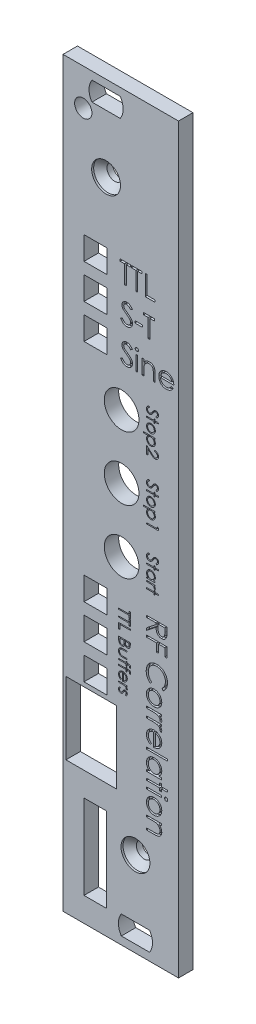
SolidWorks part; units mm, degrees
ref_plane "Front Plane" through (0, 0, 0) normal (0, 0, 1) x (1, 0, 0)
ref_plane "Top Plane" through (0, 0, 0) normal (0, 1, 0) x (1, 0, 0)
ref_plane "Right Plane" through (0, 0, 0) normal (1, 0, 0) x (0, 0, -1)
ref_plane "Plane1" through (0, 0, 2.5) normal (0, 0, 1) x (1, 0, 0)
sketch "Sketch1" plane through (0, 0, 2.5) normal (0, 0, 1) x (1, 0, 0)
  line L0 (12.53, 125.4) -> (-7.45, 125.4)
  line L1 (-7.45, 125.4) -> (-7.45, -3)
  line L2 (-7.45, -3) -> (12.53, -3)
  line L3 (12.53, -3) -> (12.53, 125.4)
  dimension "D1" = 19.98
extrude "Boss-Extrude1" add sketch "Sketch1" against normal blind 2.5
sketch "Sketch2" plane through (0, 0, 2.5) normal (0, 0, 1) x (1, 0, 0)
  line L0 (2.4454, 124.05) -> (-2.4454, 124.05)
  line L1 (-2.4454, 120.75) -> (2.4454, 120.75)
  arc A0 (-2.4454, 124.05) -> (-2.4454, 120.75) centre (0, 122.4) ccw
  arc A1 (2.4454, 120.75) -> (2.4454, 124.05) centre (0, 122.4) ccw
extrude "Cut-Extrude1" cut sketch "Sketch2" against normal through all
sketch "Sketch3" plane through (0, 0, 2.5) normal (0, 0, 1) x (1, 0, 0)
  line L0 (7.5254, 1.65) -> (2.6346, 1.65)
  line L1 (2.6346, -1.65) -> (7.5254, -1.65)
  arc A0 (2.6346, 1.65) -> (2.6346, -1.65) centre (5.08, 0) ccw
  arc A1 (7.5254, -1.65) -> (7.5254, 1.65) centre (5.08, 0) ccw
extrude "Cut-Extrude2" cut sketch "Sketch3" against normal through all
sketch "Sketch4" plane through (0, 0, 0) normal (0, 0, -1) x (-1, 0, 0)
  line L0 (3.82, 15.8) -> (-0.08, 15.8)
  line L1 (-0.08, 15.8) -> (-0.08, 1.2)
  line L2 (-0.08, 1.2) -> (3.82, 1.2)
  line L3 (3.82, 1.2) -> (3.82, 15.8)
  line L4 (7.45, 125.4) -> (7.45, -3) construction
  dimension "D1" = 3.63
extrude "Cut-Extrude3" cut sketch "Sketch4" against normal through all
hole_wizard "Ø3.0 (3) Diameter Hole1" positions "Sketch6" profile "Sketch5" hole size "Ø3.0" standard "ANSI Metric"
sketch "Sketch6" plane through (0, 0, 2.5) normal (0, 0, 1) x (1, 0, 0)
  point P0 (-3.95, 119.1)
sketch "Sketch5" plane through (-3.95, 119.1, 2.5) normal (1, 0, 0) x (0, -1, 0)
  line L0 (0, 0) -> (0, 2.5)
  line L1 (0, 2.5) -> (1.5, 2.5)
  line L2 (1.5, 2.5) -> (1.5, 0)
  line L5 (1.5, 0) -> (0, 0)
  line L11 (0, -6.35) -> (0, 107.95) construction
  dimension "Thru Hole Dia." = 3
  dimension "Thru Hole Depth" = 2.5
hole_wizard "CSK for M2.5 Flat Head Machine Screw1" positions "Sketch8" profile "Sketch7" countersink size "M2.5" standard "ANSI Metric"
sketch "Sketch8" plane through (0, 0, 2.5) normal (0, 0, 1) x (1, 0, 0)
  point P0 (5.08, 11.7)
  point P1 (0, 110.7)
sketch "Sketch7" plane through (5.08, 11.7, 2.5) normal (1, 0, 0) x (0, -1, 0)
  line L0 (0, 0) -> (0, 2.5)
  line L1 (0, 2.5) -> (1.35, 2.5)
  line L2 (1.35, 2.5) -> (1.35, 1.5)
  line L3 (1.35, 1.5) -> (2.5, 0.35)
  line L4 (2.5, 0.35) -> (2.5, 0)
  line L6 (2.5, 0) -> (0, 0)
  line L7 (-1.35, 1.5) -> (-2.5, 0.35) construction
  line L11 (0, -6.35) -> (0, 107.95) construction
  dimension "Thru Hole Dia." = 2.7
  dimension "Thru Hole Depth" = 2.5
  dimension "C'Sink Dia." = 5
  dimension "C'Sink Angle" = 90
  dimension "Head Clearance" = 0.35
ref_plane "Board bottom" through (0, 11.2, 0) normal (0, -1, 0) x (-1, 0, 0)
ref_plane "Board top" through (0, 111.2, 0) normal (0, 1, 0) x (1, 0, 0)
ref_plane "Board upper surface" through (-3.82, 0, 0) normal (1, 0, 0) x (0, 0, -1)
ref_plane "Board lower surface" through (-5.42, 0, 0) normal (1, 0, 0) x (0, 0, -1)
sketch "Sketch9" plane through (0, 0, 2.5) normal (0, 0, 1) x (1, 0, 0)
  line L0 (-3.82, 19.95) -> (-3.82, 32.45) construction
  line L1 (-3.82, 19.95) -> (1.78, 19.95)
  line L2 (-3.82, 32.45) -> (1.78, 32.45)
  line L3 (1.78, 19.95) -> (1.78, 32.45)
  line L4 (-3.82, -47.3899) -> (-3.82, 47.3899) construction
  line L5 (-28.8918, 11.2) -> (28.8918, 11.2) construction
  line L6 (-3.82, 32.45) -> (-3.82, 19.95) construction
  line L7 (-3.82, 32.45) -> (-6.95, 32.45)
  line L8 (-3.82, 19.95) -> (-6.95, 19.95)
  line L9 (-6.95, 32.45) -> (-6.95, 19.95)
  line L10 (-6.95, 32.45) -> (1.78, 19.95) construction
  line L11 (1.78, 32.45) -> (-6.95, 19.95) construction
  line L12 (-7.45, 125.4) -> (-7.45, -3) construction
  point P8 (-2.585, 26.2)
  dimension "D1" = 8.75
  dimension "D2" = 21.25
  dimension "D3" = 5.6
  dimension "D4" = 3.13
  dimension "D5" = 15
  dimension "D6" = 1.235
  dimension "D7" = 12.5
  dimension "D8" = 8.73
  dimension "D9" = 0.5
extrude "USB" cut sketch "Sketch9" against normal through all
sketch "Sketch10" plane through (0, 0, 2.5) normal (0, 0, 1) x (1, 0, 0)
  line L1 (-3.82, 37.2) -> (0.18, 37.2)
  line L2 (-3.82, 37.2) -> (-3.82, 33.2)
  line L3 (-3.82, 33.2) -> (0.18, 33.2)
  line L4 (0.18, 37.2) -> (0.18, 33.2)
  line L5 (-3.82, 37.2) -> (0.18, 33.2) construction
  line L6 (-3.82, 33.2) -> (0.18, 37.2) construction
  line L7 (-3.82, -47.3899) -> (-3.82, 47.3899) construction
  line L8 (-1.82, 35.2) -> (0.18, 35.2) construction
  line L9 (-28.8918, 11.2) -> (28.8918, 11.2) construction
  point P0 (-1.82, 35.2)
  dimension "D1" = 4
  dimension "D2" = 4
  dimension "D3" = 24
  dimension "D4" = 0
extrude "MCXX" cut sketch "Sketch10" against normal through all
pattern_linear "Copy MMCX 1" count 3 spacing 6 along (0, 1, 0) of "MCXX"
pattern_linear "Copy MMCX 2" count 2 spacing 51 along (0, 1, 0) of "Copy MMCX 1"
sketch "Sketch12" plane through (0, 0, 2.5) normal (0, 0, 1) x (1, 0, 0)
  line L0 (-3.82, -47.3899) -> (-3.82, 47.3899) construction
  line L1 (-28.8918, 11.2) -> (28.8918, 11.2) construction
  circle A0 centre (2.68, 55.2) radius 3
  dimension "D1" = 6
  dimension "D2" = 6.5
  dimension "D3" = 44
extrude "Selector 1" cut sketch "Sketch12" against normal through all
pattern_linear "Copy selector" count 3 spacing 11 along (0, 1, 0) of "Selector 1"
sketch "Sketch13" plane through (0, 0, 2.5) normal (0, 0, 1) x (1, 0, 0)
  line L0 (-3.82, 96.2) -> (0.18, 96.2) construction
  line L1 (0.18, 96.2) -> (0.18, 100.2) construction
  text T0 "TTL"
  dimension "D1" = 2.2
extrude "Text TTL" cut sketch "Sketch13" against normal blind 0.5
sketch "Sketch14" plane through (0, 0, 2.5) normal (0, 0, 1) x (1, 0, 0)
  line L7 (-3.82, 90.2) -> (0.18, 90.2) construction
  line L8 (2.4249, 99.341) -> (2.4249, 99.7) construction
  text T0 "S-T"
extrude "Text ST" cut sketch "Sketch14" against normal blind 0.5
sketch "Sketch15" plane through (0, 0, 2.5) normal (0, 0, 1) x (1, 0, 0)
  line L0 (-3.82, 84.2) -> (0.18, 84.2) construction
  line L1 (2.4249, 99.341) -> (2.4249, 99.7) construction
  text T0 "Sine"
extrude "Text Sine" cut sketch "Sketch15" against normal blind 0.5
ref_plane "Text align 2" through (7.03, 0, 0) normal (1, 0, 0) x (0, 0, -1)
sketch "Sketch17" plane through (0, 0, 2.5) normal (0, 0, 1) x (1, 0, 0)
  line L1 (2.68, 69.2) -> (7.03, 69.2) construction
  line L2 (7.03, -1.375) -> (7.03, 1.375) construction
  line L3 (7.03, 69.2) -> (7.03, 59.5505) construction
  circle A0 centre (2.68, 66.2) radius 3 construction
  text T0 "Stop1" font "Century Gothic" height 2
extrude "Cut-Extrude11" cut sketch "Sketch17" against normal blind 0.5
sketch "Sketch18" plane through (0, 0, 2.5) normal (0, 0, 1) x (1, 0, 0)
  line L0 (2.68, 58.2) -> (7.03, 58.2) construction
  line L1 (7.03, -1.375) -> (7.03, 1.375) construction
  line L2 (7.03, 58.2) -> (7.03, 47.8465) construction
  circle A0 centre (2.68, 55.2) radius 3 construction
  text T0 "Start" font "Century Gothic" height 2
extrude "Cut-Extrude12" cut sketch "Sketch18" against normal blind 0.5
sketch "Sketch21" plane through (0, 0, 2.5) normal (0, 0, 1) x (1, 0, 0)
  line L0 (2.68, 80.2) -> (7.03, 80.2) construction
  line L1 (7.03, -1.375) -> (7.03, 1.375) construction
  line L2 (7.03, 80.2) -> (7.03, 70.7585) construction
  circle A0 centre (2.68, 77.2) radius 3 construction
  text T0 "Stop2" font "Century Gothic" height 2
extrude "Cut-Extrude14" cut sketch "Sketch21" against normal blind 0.5
sketch "Sketch23" plane through (0, 0, 2.5) normal (0, 0, 1) x (1, 0, 0)
  line L0 (2.18, 49.2) -> (2.18, 33.2) construction
  line L1 (0.18, 33.2) -> (0.18, 37.2) construction
  line L2 (-3.82, 33.2) -> (0.18, 33.2) construction
  line L3 (0.18, 49.2) -> (-3.82, 49.2) construction
  line L4 (0.18, 39.2) -> (0.18, 43.2) construction
  text T0 "TTL Buffers" font "Century Gothic" height 2
  dimension "D1" = 2
extrude "Cut-Extrude15" cut sketch "Sketch23" against normal blind 0.5
sketch "Sketch24" plane through (0, 0, 2.5) normal (0, 0, 1) x (1, 0, 0)
  line L0 (7.03, 49.2) -> (7.03, 15.9676) construction
  line L1 (7.03, -1.375) -> (7.03, 1.375) construction
  line L2 (0.18, 49.2) -> (-3.82, 49.2) construction
  text T0 "RF Correlation"
extrude "Main title" cut sketch "Sketch24" against normal blind 0.5
equation "\"D6@Sketch9\"=2.47/2"
